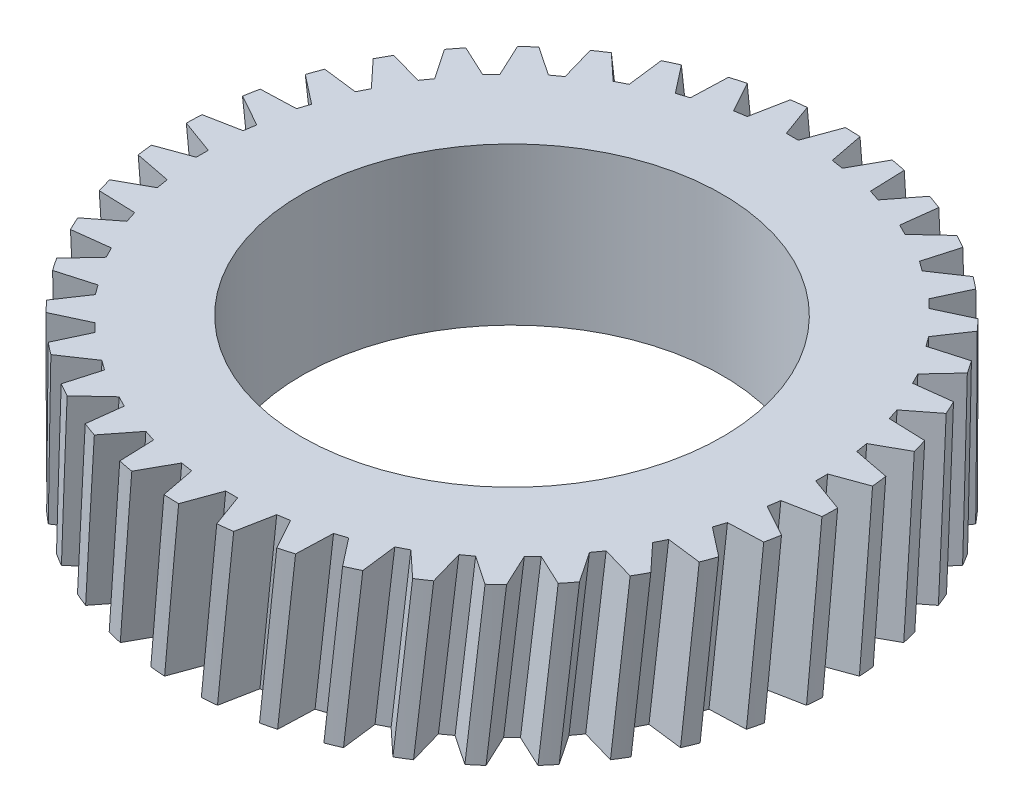
SolidWorks part; units mm, degrees
ref_plane "Спереди" through (0, 0, 0) normal (0, 0, 1) x (1, 0, 0)
ref_plane "Сверху" through (0, 0, 0) normal (0, 1, 0) x (1, 0, 0)
ref_plane "Справа" through (0, 0, 0) normal (1, 0, 0) x (0, 0, -1)
sketch "Эскиз1" plane through (0, 0, 0) normal (0, 1, 0) x (1, 0, 0)
  circle A0 centre (0, 0) radius 31.5
  circle A1 centre (0, 0) radius 20.1
  dimension "D1" = 40.2
  dimension "63" = 63
extrude "Бобышка-Вытянуть1" add sketch "Эскиз1" along normal blind 15
sketch "Эскиз7" plane through (0, 0, 0) normal (0, 1, 0) x (1, 0, 0)
  line L0 (0, 0) -> (32, 0) construction
  line L1 (28.2, -0.5719) -> (28.2, 0.5719)
  line L2 (32, -1.955) -> (32, 1.955)
  line L3 (28.2, 0.5719) -> (32, 1.955)
  line L4 (28.2, -0.5719) -> (32, -1.955)
  line L5 (30, 1.2271) -> (30, -1.2271) construction
  dimension "D1" = 32
  dimension "D2" = 28.2
  dimension "D3" = 20
  dimension "D4" = 3.91
  dimension "D5" = 30
ref_plane "Плоскость6" through (30, 0, 0) normal (1, 0, 0) x (0, 0, -1)
sketch "Эскиз8" plane through (30, 0, 0) normal (1, 0, 0) x (0, 0, -1)
  line L0 (0, 0) -> (0, 15) construction
  line L1 (31.5, 15) -> (-31.5, 15) construction
  line L2 (0, 0) -> (1.6102, 17.1938)
  dimension "D1" = 5.35
sweep "Вырез-По траектории4" cut profiles "Эскиз7" path "Эскиз8"
pattern_circular "Круговой массив4" count 40 over 360 about axis through (0, 15, 0) along (0, -1, 0) of "Вырез-По траектории4"
